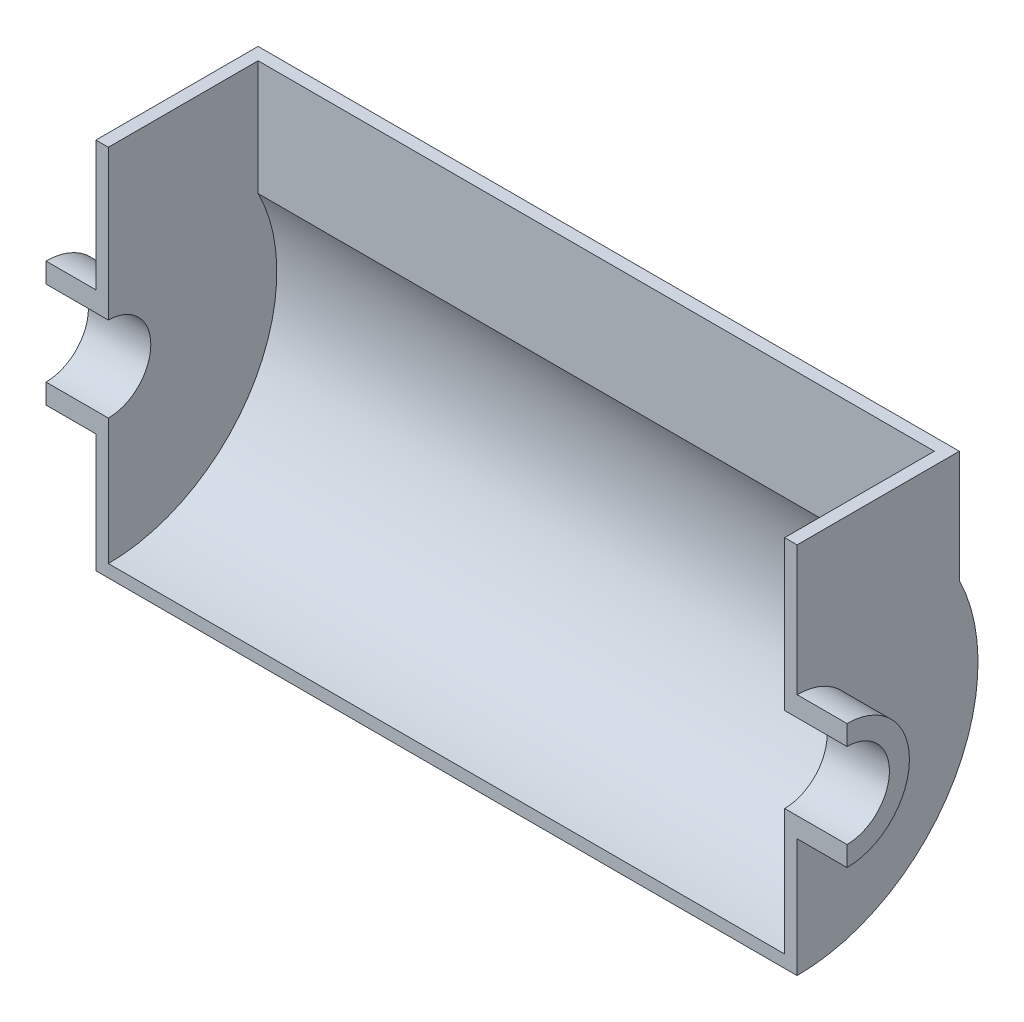
SolidWorks part; units mm, degrees
ref_plane "Front Plane" through (0, 0, 0) normal (0, 0, 1) x (1, 0, 0)
ref_plane "Top Plane" through (0, 0, 0) normal (0, 1, 0) x (1, 0, 0)
ref_plane "Right Plane" through (0, 0, 0) normal (1, 0, 0) x (0, 0, -1)
sketch "Sketch1" plane through (0, 0, 0) normal (1, 0, 0) x (0, 0, -1)
  line L0 (0, -25) -> (0, -17)
  line L1 (0, 17) -> (0, 25)
  line L2 (0, 25) -> (0, 77)
  line L3 (0, 77) -> (65, 77)
  line L4 (65, 77) -> (65, 32)
  line L5 (0, -25) -> (0, -72.5)
  arc A0 (0, -17) -> (0, 17) centre (0, 0) ccw
  arc A1 (0, -25) -> (0, 25) centre (0, 0) ccw
  arc A2 (0, -72.5) -> (65, 32.1131) centre (0, 0) ccw
  point P7 (0, 0)
  dimension "D1" = 17
  dimension "D2" = 25
  dimension "D6" = 72.5
  dimension "D3" = 60
  dimension "D4" = 65
  dimension "D5" = 45
extrude "Boss-Extrude1" add sketch "Sketch1" along normal blind 20 and the other way blind 5 contours L0 A0 L1 A1
extrude "Boss-Extrude2" add sketch "Sketch1<3>" against normal blind 5 separate body contours L5 A2 L4 L3 L2 A1 region at (0, 8.1353, -34.9191)
sketch "Sketch1<3>" plane through (0, 0, 0) normal (1, 0, 0) x (0, 0, -1) same geometry as "Sketch1"
sketch "Sketch3" plane through (-5, 0, 0) normal (-1, 0, 0) x (0, 0, 1)
  line L0 (-60, 77) -> (-60, 30.9233)
  line L4 (0, -72.5) -> (0, -25)
  line L5 (0, 25) -> (0, 77)
  line L6 (0, 77) -> (-65, 77)
  line L7 (-65, 77) -> (-65, 32.1131)
  line L8 (0, -72.5) -> (0, -67.5)
  line L10 (-60, 77) -> (-65, 77)
  line L11 (-65, 77) -> (-65, 32.1131)
  line L12 (-5, 29.5804) -> (-5, 72) construction
  line L13 (-5, -67.3146) -> (-5, -29.5804) construction
  line L15 (-60, 72) -> (-60, 30.9233) construction
  line L16 (-5, 72) -> (-60, 72) construction
  line L17 (0, 77) -> (-65, 77) construction
  line L18 (0, 25) -> (0, 77) construction
  line L19 (0, -72.5) -> (0, -25) construction
  arc A0 (-60, 30.9233) -> (0, -67.5) centre (0, 0) ccw
  arc A2 (0, 25) -> (0, -25) centre (0, 0) ccw
  arc A3 (-65, 32.1131) -> (0, -72.5) centre (0, 0) ccw
  arc A5 (-65, 32.1131) -> (0, -72.5) centre (0, 0) ccw
  arc A6 (-5, 29.5804) -> (-5, -29.5804) centre (0, 0) ccw construction
  arc A7 (-60, 30.9233) -> (-5, -67.3146) centre (0, 0) ccw construction
  arc A8 (0, 25) -> (0, -25) centre (0, 0) ccw construction
  dimension "D1" = 0
  dimension "D2" = 5
extrude "Boss-Extrude3" add sketch "Sketch3" along normal blind 271
sketch "Sketch5" plane through (-276, 0, 0) normal (-1, 0, 0) x (0, 0, 1)
  line L0 (0, -72.5) -> (0, -67.5) construction
  line L1 (-60, 30.9233) -> (-60, 77) construction
  line L2 (-60, 77) -> (-65, 77) construction
  line L3 (-65, 77) -> (-65, 32.1131) construction
  line L4 (-60, 77) -> (-60, 30.9233) construction
  line L5 (0, -67.5) -> (0, -17) construction
  line L6 (0, 17) -> (0, 77) construction
  line L7 (0, 77) -> (-60, 77) construction
  line L8 (0, -72.5) -> (0, -67.5)
  line L9 (-60, 30.9233) -> (-60, 77)
  line L10 (-60, 77) -> (-65, 77)
  line L11 (-65, 77) -> (-65, 32.1131)
  line L12 (-60, 77) -> (-60, 30.9233)
  line L13 (0, -67.5) -> (0, -17)
  line L14 (0, 17) -> (0, 77)
  line L15 (0, 77) -> (-60, 77)
  arc A0 (-65, 32.1131) -> (0, -72.5) centre (0, 0) ccw construction
  arc A1 (-60, 30.9233) -> (0, -67.5) centre (0, 0) ccw construction
  arc A2 (-60, 30.9233) -> (0, -67.5) centre (0, 0) ccw construction
  arc A3 (0, 17) -> (0, -17) centre (0, 0) ccw construction
  arc A4 (-65, 32.1131) -> (0, -72.5) centre (0, 0) ccw
  arc A5 (-60, 30.9233) -> (0, -67.5) centre (0, 0) ccw
  arc A6 (-60, 30.9233) -> (0, -67.5) centre (0, 0) ccw
  arc A7 (0, 17) -> (0, -17) centre (0, 0) ccw
  arc A8 (0, 25) -> (0, -25) centre (0, 0) ccw
  arc M1 (-65, 32.1131) -> (0, -72.5) centre (0, 0) ccw
  line M2 (0, -72.5) -> (0, -67.5)
  arc M3 (0, -67.5) -> (-60, 30.9233) centre (0, 0) cw
  line M4 (-60, 30.9233) -> (-60, 77)
  line M5 (-60, 77) -> (-65, 77)
  line M6 (-65, 77) -> (-65, 32.1131)
  dimension "D1" = 25
extrude "Boss-Extrude4" add sketch "Sketch5" along normal blind 5 contours A8 L14 L15 L13 M4 M3 | M6 M1 M2 M3 M4 M5 region at (-276, -37.3857, -60.1698) region at (-276, 10.4681, -32.6259)
extrude "Boss-Extrude5" add sketch "Sketch5<4>" along normal blind 25 contours L14 A8 L13 A7 region at (-276, 0, -24.441)
sketch "Sketch5<4>" plane through (-276, 0, 0) normal (-1, 0, 0) x (0, 0, 1) same geometry as "Sketch5"
sketch "Sketch6" plane through (0, 0, 0) normal (0, 0, 1) x (1, 0, 0)
